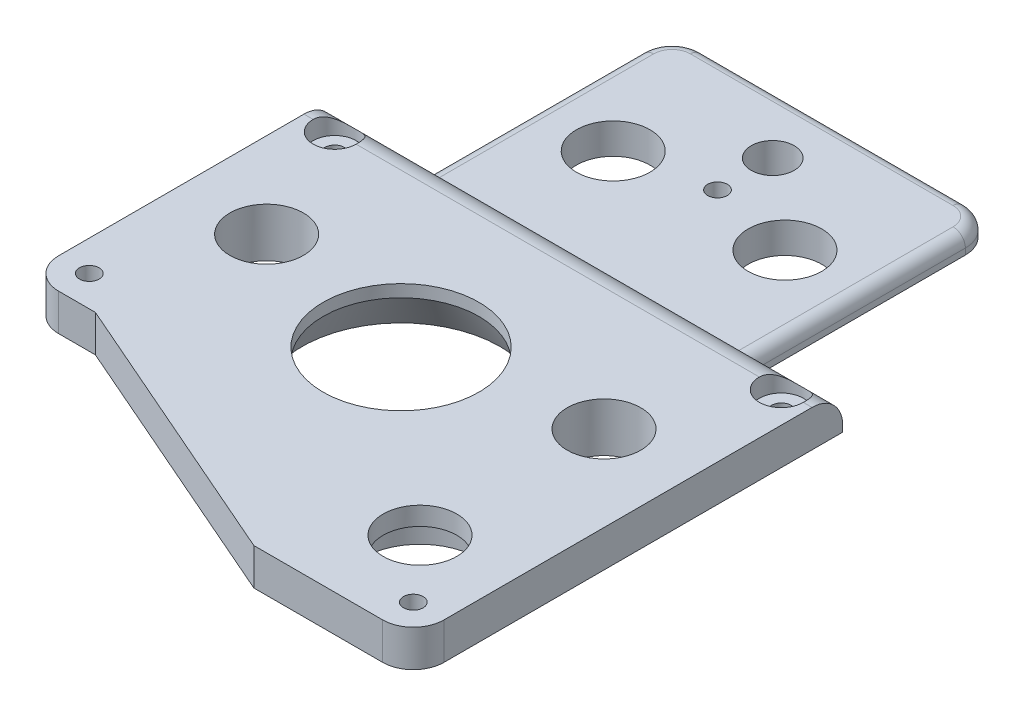
SolidWorks part; units mm, degrees
ref_plane "Спереди" through (0, 0, 0) normal (0, 0, 1) x (1, 0, 0)
ref_plane "Сверху" through (0, 0, 0) normal (0, 1, 0) x (1, 0, 0)
ref_plane "Справа" through (0, 0, 0) normal (1, 0, 0) x (0, 0, -1)
sketch "Sketch1" plane through (0, 0, 0) normal (0, 1, 0) x (1, 0, 0)
  line L0 (-26.4129, 15) -> (-26.4129, 55)
  line L1 (-26.4129, 55) -> (26.4129, 55)
  line L2 (26.4129, 55) -> (26.4129, 15)
  line L3 (26.4129, 15) -> (41.4129, 15)
  line L4 (41.4129, 15) -> (41.4129, -55)
  line L5 (41.4129, -55) -> (15.4129, -55)
  line L6 (15.4129, -55) -> (-30.4129, -35)
  line L7 (-30.4129, -35) -> (-41.4129, -35)
  line L8 (-41.4129, -35) -> (-41.4129, 15)
  line L9 (-41.4129, 15) -> (-26.4129, 15)
  dimension "D1" = 50
  dimension "D2" = 70
  dimension "D3" = 26
  dimension "D4" = 40
  dimension "D5" = 11
  dimension "D6" = 50
  dimension "D7" = 15
extrude "Boss-Extrude1" add sketch "Sketch1" along normal blind 3
sketch "Sketch2" plane through (0, 0, 0) normal (0, -1, 0) x (1, 0, 0)
  line L0 (-38.1629, 31.75) -> (-38.1629, -11.75)
  line L1 (-38.1629, -11.75) -> (-23.1629, -11.75)
  line L2 (-23.1629, -11.75) -> (-23.1629, -51.75)
  line L3 (-23.1629, -51.75) -> (23.1629, -51.75)
  line L4 (23.1629, -51.75) -> (23.1629, -11.75)
  line L5 (23.1629, -11.75) -> (38.1629, -11.75)
  line L6 (38.1629, -11.75) -> (38.1629, 51.75)
  line L7 (38.1629, 51.75) -> (16.0912, 51.75)
  line L8 (16.0912, 51.75) -> (-29.7346, 31.75)
  line L9 (-29.7346, 31.75) -> (-38.1629, 31.75)
  line L10 (-41.4129, 35) -> (-30.4129, 35) construction
  line L11 (-41.4129, -15) -> (-41.4129, 35) construction
  line L12 (-26.4129, -55) -> (-26.4129, -15) construction
  line L13 (26.4129, -55) -> (-26.4129, -55) construction
  line L14 (26.4129, -15) -> (26.4129, -55) construction
  line L15 (15.4129, 55) -> (41.4129, 55) construction
  line L18 (-30.4129, 35) -> (15.4129, 55) construction
  line L19 (41.4129, 55) -> (41.4129, -15) construction
  line L20 (-26.4129, -15) -> (-41.4129, -15) construction
  line L21 (41.4129, -15) -> (26.4129, -15) construction
  dimension "D1" = 3.25
  dimension "D2" = 3.25
  dimension "D3" = 3.25
  dimension "D4" = 3.25
  dimension "D5" = 3.25
  dimension "D6" = 3.25
  dimension "D7" = 3.25
  dimension "D8" = 3.25
  dimension "D9" = 3.25
  dimension "D10" = 3.25
extrude "Boss-Extrude2" add sketch "Sketch2" along normal blind 2
chamfer "Chamfer1" distance 2 angle 10 10 edges at (-33.9487, -2, 31.75) (-6.8217, -2, 41.75) (27.127, -2, 51.75) (38.1629, -2, 20) (30.6629, -2, -11.75) (23.1629, -2, -31.75) (0, -2, -51.75) (-23.1629, -2, -31.75) (-30.6629, -2, -11.75) (-38.1629, -2, 10) first distance on face at (-33.9487, -1, 31.75) first distance on face at (-6.8217, -1, 41.75) first distance on face at (27.127, -1, 51.75) first distance on face at (38.1629, -1, 20) first distance on face at (30.6629, -1, -11.75) first distance on face at (23.1629, -1, -31.75) first distance on face at (0, -1, -51.75) first distance on face at (-23.1629, -1, -31.75) first distance on face at (-30.6629, -1, -11.75) first distance on face at (-38.1629, -1, 10)
sketch "Sketch3" plane through (0, 3, 0) normal (0, 1, 0) x (1, 0, 0)
  line L0 (-26.4129, 33) -> (26.4129, 33) construction
  line L1 (-26.4129, 55) -> (-26.4129, 15) construction
  line L2 (26.4129, 15) -> (26.4129, 55) construction
  line L3 (26.4129, 55) -> (-26.4129, 55) construction
  line L4 (0, 33) -> (0, 55) construction
  line L5 (-26.4129, 15) -> (26.4129, 15) construction
  line L6 (0, 15) -> (0, 55) construction
  line L7 (0, 30) -> (0, 40) construction
  line L8 (5, 30) -> (-5, 30) construction
  line L9 (5, 30) -> (5, 40) construction
  line L10 (5, 40) -> (-5, 40) construction
  line L11 (-5, 30) -> (-5, 40) construction
  line L12 (5, 30) -> (-5, 40) construction
  line L13 (5, 40) -> (-5, 30) construction
  circle A0 centre (-14, 33) radius 6
  circle A1 centre (14, 33) radius 6
  circle A2 centre (0, 45) radius 3.5
  circle A3 centre (0, 36) radius 1.6
  point P10 (0, 33)
  point P25 (0, 35)
  dimension "D1" = 28
  dimension "D2" = 12
  dimension "D5" = 7
  dimension "D9" = 3.2
  dimension "D3" = 14
  dimension "D4" = 22
  dimension "D6" = 10
  dimension "D7" = 15
  dimension "D8" = 10
  dimension "D10" = 4
extrude "Cut-Extrude1" cut sketch "Sketch3" against normal through all
sketch "Sketch4" plane through (0, 3, 0) normal (0, 1, 0) x (1, 0, 0)
  line L0 (-41.4129, 15) -> (41.4129, 15)
  line L1 (41.4129, 15) -> (41.4129, -55)
  line L2 (41.4129, -55) -> (15.4129, -55)
  line L3 (15.4129, -55) -> (-30.4129, -35)
  line L4 (-30.4129, -35) -> (-41.4129, -35)
  line L5 (-41.4129, -35) -> (-41.4129, 15)
extrude "Boss-Extrude3" add sketch "Sketch4" along normal blind 3
fillet "Fillet1" radius 5 1 edges at (0, 6, -15)
sketch "Sketch6" plane through (0, 6, 0) normal (0, 1, 0) x (1, 0, 0)
  line L0 (-41.4129, -15) -> (41.4129, -15) construction
  line L1 (-41.4129, 10) -> (-41.4129, -35) construction
  line L2 (41.4129, -55) -> (41.4129, 10) construction
  line L3 (15.4129, -55) -> (41.4129, -55) construction
  line L4 (-41.4129, -10) -> (41.4129, -10) construction
  line L5 (-41.4129, -35) -> (-30.4129, -35) construction
  line L6 (27.5, -10) -> (27.5, -55) construction
  circle A0 centre (-0.5871, -15) radius 12.7
  circle A1 centre (-27.5, -10) radius 6
  circle A2 centre (27.5, -10) radius 6
  circle A3 centre (27.5, -40) radius 6
  point P16 (0, -10)
  dimension "D1" = 25.4
  dimension "D4" = 12
  dimension "D9" = 12
  dimension "D2" = 42
  dimension "D3" = 40
  dimension "D5" = 55
  dimension "D6" = 27.5
  dimension "D7" = 25
  dimension "D8" = 30
extrude "Cut-Extrude3" cut sketch "Sketch6" against normal up to next
sketch "Sketch7" plane through (0, -2, 0) normal (0, -1, 0) x (1, 0, 0)
  circle A0 centre (27.5, 40) radius 9.5
  dimension "D2" = 19
extrude "Cut-Extrude4" cut sketch "Sketch7" against normal blind 5
chamfer "Chamfer2" distance 6 angle 30 1 edges at (-0.5871, -2, 2.3) first distance on face at (-0.5871, -2, 2.3)
fillet "Fillet2" radius 5 4 edges at (-41.4129, 3, 35) (41.4129, 3, 55) (26.4129, 1.5, -55) (-26.4129, 1.5, -55)
fillet "Fillet3" radius 2 5 edges at (26.4129, 3, -32.2913) (24.9484, 3, -53.5355) (0, 3, -55) (-24.9484, 3, -53.5355) (-26.4129, 3, -32.2913)
sketch "Sketch9" plane through (0, 6, 0) normal (0, 1, 0) x (1, 0, 0)
  line L0 (15.4129, -55) -> (36.4129, -55) construction
  line L1 (41.4129, -50) -> (41.4129, 10) construction
  line L2 (-41.4129, 10) -> (-41.4129, -30) construction
  line L3 (-36.4129, -35) -> (-30.4129, -35) construction
  line L4 (-41.4129, 15) -> (-26.4129, 15) construction
  line L5 (26.4129, 15) -> (41.4129, 15) construction
  circle A0 centre (36.4129, -50) radius 1.6
  circle A1 centre (-36.4129, -30) radius 1.6
  circle A2 centre (36.4129, 10) radius 1.6
  circle A3 centre (-36.4129, 10) radius 1.6
  dimension "D1" = 3.2
  dimension "D2" = 5
  dimension "D3" = 5
  dimension "D4" = 5
  dimension "D5" = 5
  dimension "D6" = 5
  dimension "D7" = 5
  dimension "D8" = 5
  dimension "D9" = 5
extrude "Cut-Extrude5" cut sketch "Sketch9" against normal through all
sketch "Sketch10" plane through (0, 6, 0) normal (0, 1, 0) x (1, 0, 0)
  circle A0 centre (-36.4129, 10) radius 3.5
  circle A1 centre (36.4129, 10) radius 3.5843
  dimension "D1" = 7
extrude "Cut-Extrude6" cut sketch "Sketch10" against normal blind 3
sketch "Sketch11" plane through (0, -2, 0) normal (0, -1, 0) x (1, 0, 0)
  line L0 (-32.7629, -11.75) -> (-32.7629, -6.35)
  line L2 (-32.7629, -6.35) -> (-38.1629, -6.35)
  line L3 (-38.1629, -11.75) -> (-23.1629, -11.75) construction
  line L4 (-38.1629, -6.35) -> (-38.1629, -11.75)
  line L5 (-38.1629, -11.75) -> (-32.7629, -11.75)
  line L6 (-38.1629, 26.35) -> (-32.7629, 26.35)
  line L7 (-32.7629, 26.35) -> (-32.7629, 31.75)
  line L9 (-32.7629, 31.75) -> (-38.1629, 31.75)
  line L10 (-38.1629, 31.75) -> (-38.1629, 26.35)
  line L11 (-23.1629, -51.75) -> (-23.1629, -46.35)
  line L12 (-29.7346, 31.75) -> (-38.1629, 31.75) construction
  line L13 (-23.1629, -46.35) -> (-17.7629, -46.35)
  line L14 (-17.7629, -46.35) -> (-17.7629, -51.75)
  line L16 (-17.7629, -51.75) -> (-23.1629, -51.75)
  line L17 (23.1629, -51.75) -> (17.7629, -51.75)
  line L18 (17.7629, -51.75) -> (17.7629, -46.35)
  line L19 (17.7629, -46.35) -> (23.1629, -46.35)
  line L20 (38.1629, 51.75) -> (16.0912, 51.75) construction
  line L21 (23.1629, -46.35) -> (23.1629, -51.75)
  line L22 (38.1629, -11.75) -> (32.7629, -11.75)
  line L24 (32.7629, -11.75) -> (32.7629, -6.35)
  line L25 (32.7629, -6.35) -> (38.1629, -6.35)
  line L27 (38.1629, -6.35) -> (38.1629, -11.75)
  line L28 (38.1629, 46.35) -> (32.7629, 46.35)
  line L29 (32.7629, 46.35) -> (32.7629, 51.75)
  line L31 (32.7629, 51.75) -> (38.1629, 51.75)
  line L32 (38.1629, 51.75) -> (38.1629, 46.35)
  line L33 (38.1629, -11.75) -> (38.1629, 51.75) construction
  line L34 (-38.1629, 31.75) -> (-38.1629, -11.75) construction
  line L36 (23.1629, -51.75) -> (23.1629, -11.75) construction
  line L37 (-23.1629, -11.75) -> (-23.1629, -51.75) construction
  line L38 (23.1629, -11.75) -> (38.1629, -11.75) construction
  line L39 (-23.1629, -51.75) -> (23.1629, -51.75) construction
  dimension "D1" = 5.4
extrude "Cut-Extrude7" cut sketch "Sketch11" against normal up to surface (2 mm away) up to face at (-1.0714, 0, -0.7143)
